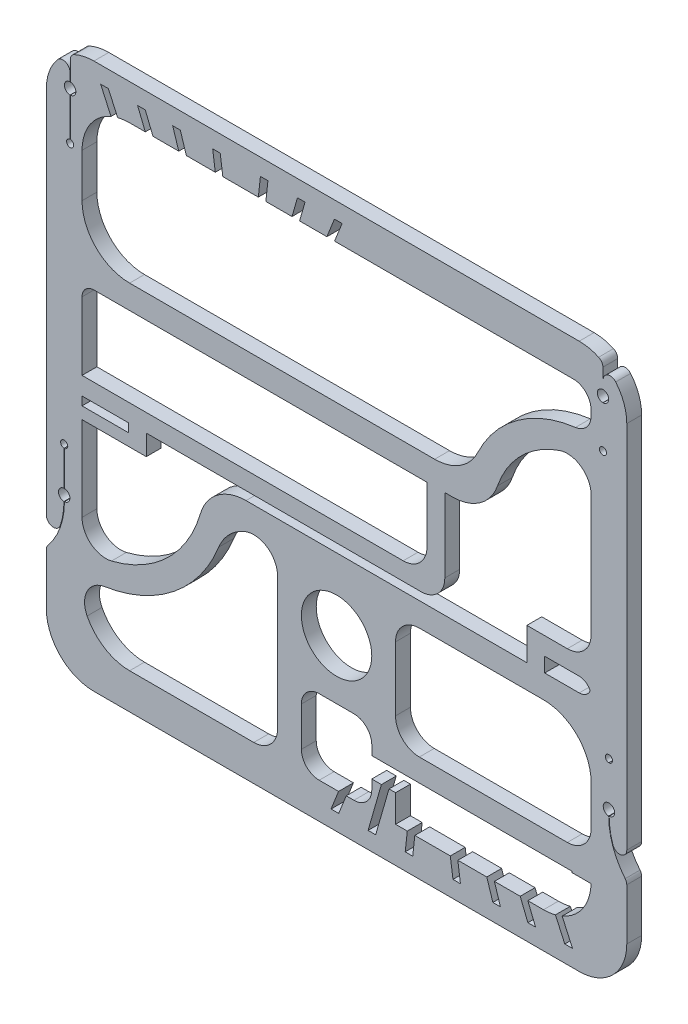
SolidWorks part; units mm, degrees
ref_plane "Front Plane" through (0, 0, 0) normal (0, 0, 1) x (1, 0, 0)
ref_plane "Top Plane" through (0, 0, 0) normal (0, 1, 0) x (1, 0, 0)
ref_plane "Right Plane" through (0, 0, 0) normal (1, 0, 0) x (0, 0, -1)
sketch "Sketch1" plane through (0, 0, 0) normal (0, 0, 1) x (1, 0, 0)
  line L0 (44.642, 21.8842) -> (44.642, 18.0742) construction
  line L1 (-10.1934, 21.8842) -> (51.7832, 21.8842)
  line L2 (-10.1934, 21.8842) -> (-10.1934, -36.406)
  line L3 (-10.1934, -36.406) -> (51.7832, -36.406)
  line L4 (51.7832, 21.8842) -> (51.7832, -36.406)
  line L5 (47.9732, -32.596) -> (-6.3834, -32.596)
  line L6 (47.9732, -32.596) -> (47.9732, 18.0742)
  line L7 (47.9732, 18.0742) -> (-6.3834, 18.0742)
  line L8 (-6.3834, -32.596) -> (-6.3834, 18.0742)
  line L9 (44.642, 19.9792) -> (-35.1587, 19.9792) construction
  line L10 (-6.3834, -31.0517) -> (-10.1934, -31.0517) construction
  line L11 (-8.2884, -31.0517) -> (-8.2884, 6.9585) construction
  line L12 (20.6521, 19.9792) -> (21.1982, 19.9792) construction
  line L14 (3.0779, -32.596) -> (3.0779, -36.406) construction
  line L15 (3.0779, -34.501) -> (37.3423, -34.501) construction
  line L16 (47.9732, -11.8991) -> (47.9732, 12.9942) construction
  line L17 (51.7832, 15.2205) -> (47.9732, 15.2205) construction
  line L18 (49.8782, 15.2205) -> (49.8782, -0.9437) construction
  line L20 (20.9378, -34.501) -> (20.3916, -34.501) construction
  line L21 (-6.3834, 8.0412) -> (-6.3834, -11.8991) construction
  dimension "D1" = 3.81
  dimension "D2" = 3.81
extrude "Boss-Extrude1" add sketch "Sketch1" along normal blind 1.5875
sketch "Sketch2" plane through (0, 0, 0) normal (0, 0, -1) x (-1, 0, 0)
  line L0 (-47.9732, -32.596) -> (-47.9732, 18.0742) construction
  line L1 (-34.8696, 3.2518) -> (6.3834, 3.2518)
  line L2 (-47.9732, 3.653) -> (-47.9732, 0.4065)
  line L3 (-37.4096, 0.7118) -> (6.3834, 0.7118)
  line L4 (6.3834, 3.2518) -> (6.3834, 0.7118)
  line L5 (6.3834, 18.0742) -> (6.3834, -32.596) construction
  line L8 (-47.9732, -13.182) -> (-9.1041, -13.182)
  line L9 (-47.9732, -13.182) -> (-47.9732, -10.642)
  line L10 (-47.9732, -10.642) -> (-6.771, -10.642)
  line L11 (1.357, -21.2563) -> (14.2432, -21.2563) construction
  line L12 (6.3834, -23.7963) -> (6.3834, -26.3363)
  line L13 (-47.9732, 13.8154) -> (-47.9732, 11.2754)
  line L14 (-41.1149, -10.642) -> (-0.4749, -10.642) construction
  line L15 (-40.2005, -1.1932) -> (-39.5655, -1.1932) construction
  arc A0 (-47.9732, 11.2754) -> (-37.4096, 0.7118) centre (-47.9732, 0.7118) cw
  arc A1 (-47.9732, 13.8154) -> (-34.8696, 3.2518) centre (-47.9732, 0.4065) cw
  arc A2 (6.3834, -23.7963) -> (-6.771, -10.642) centre (6.3834, -10.642) cw
  arc A3 (-9.1041, -13.182) -> (6.3834, -26.3363) centre (6.3834, -10.642) ccw
  circle A5 centre (1.357, -18.2591) radius 2.9972 construction
  line M5 (-47.9732, -32.596) -> (-47.9732, 18.0742)
  line M7 (6.3834, 18.0742) -> (6.3834, -32.596)
  dimension "D5" = 2.54
  dimension "D1" = 2.54
  dimension "D2" = 2.54
  dimension "D3" = 2.54
  dimension "D4" = 2.54
  dimension "D6" = 2.54
  dimension "D7" = 2.54
  dimension "D8" = 1.905
extrude "Boss-Extrude2" add sketch "Sketch2" against normal up to surface (1.5875 mm away) contours A1 A0 L3 L1 M5 M7 | L10 L8 M5 M7 region at (14.2431, 2.6927, 0) region at (-5.8176, -25.0663, 0) up to face at (20.7949, -7.2609, 1.5875)
sketch "Sketch3" plane through (0, 0, 0) normal (0, 0, -1) x (-1, 0, 0)
  line L0 (-47.9732, -7.1876) -> (-41.1149, -7.1876)
  line L1 (-47.9732, -10.642) -> (-47.9732, 11.2754) construction
  line L3 (-41.1149, -7.1876) -> (-41.1149, -10.642)
  line L4 (-47.9732, -10.642) -> (-6.771, -10.642) construction
  line L5 (-41.1149, -10.642) -> (-43.0199, -10.642)
  line L6 (-43.0199, -10.642) -> (-43.0199, -9.0926)
  line L7 (-43.0199, -9.0926) -> (-47.9732, -9.0926)
  line L8 (-47.9732, -9.0926) -> (-47.9732, -7.1876)
  line L10 (-32.3519, 0.7118) -> (-32.3519, -9.7276)
  line L11 (-37.4096, 0.7118) -> (6.3834, 0.7118) construction
  line L13 (-32.3519, -9.7276) -> (6.3834, -9.7276)
  line L14 (6.3834, 0.7118) -> (6.3834, -23.7963) construction
  line L15 (6.3834, -9.7276) -> (6.3834, -7.8226)
  line L16 (6.3834, -7.8226) -> (-30.4469, -7.8226)
  line L17 (-30.4469, -7.8226) -> (-30.4469, 0.7118)
  line L18 (-30.4469, 0.7118) -> (-32.3519, 0.7118)
  line L19 (-0.4749, -9.7276) -> (-41.1149, -9.7276) construction
  line L20 (-33.6219, -7.1876) -> (-33.6219, -9.7276) construction
  line L21 (-41.1149, -9.7276) -> (-41.1149, -10.642) construction
  dimension "D1" = 1.905
  dimension "D2" = 1.905
  dimension "D3" = 2.54
  dimension "D4" = 1.905
  dimension "D5" = 1.27
  dimension "D6" = 1.905
extrude "Boss-Extrude3" add sketch "Sketch3" against normal up to surface (1.5875 mm away) up to face at (21.3162, -5.4863, 1.5875)
fillet "Fillet1" radius 5.08 4 edges at (51.7832, -36.406, 0.7937) (-10.1934, -36.406, 0.7937) (-10.1934, 21.8842, 0.7937) (51.7832, 21.8842, 0.7937)
fillet "Fillet2" radius 5.08 9 edges at (9.1041, -13.182, 0.7937) (47.9732, -13.182, 0.7937) (47.9732, -32.596, 0.7937) (-6.3834, -32.596, 0.7937) (34.8696, 3.2518, 0.7937) (-6.3834, 3.2518, 0.7937) (-6.3834, 18.0742, 0.7937) (6.771, -10.642, 0.7937) (37.4096, 0.7118, 0.7937)
fillet "Fillet3" radius 2.54 6 edges at (47.9732, -7.1876, 0.7937) (30.4469, -7.8226, 0.7937) (32.3519, -9.7276, 0.7937) (47.9732, 11.2754, 0.7937) (-6.3834, -26.3363, 0.7937) (-6.3834, -23.7963, 0.7937)
fillet "Fillet4" radius 1.27 3 edges at (47.9732, -10.642, 0.7937) (47.9732, -9.0926, 0.7937) (-6.3834, 0.7118, 0.7937)
sketch "Sketch5" plane through (0, 0, 0) normal (0, 0, -1) x (-1, 0, 0)
  line L0 (-42.8932, -13.182) -> (-12.943, -13.182) construction
  line L1 (-27.0941, -13.182) -> (-14.4957, -13.182)
  line L2 (-27.0941, -13.182) -> (-27.0941, -32.596)
  line L3 (-27.0941, -32.596) -> (-14.4957, -32.596)
  line L4 (-14.4957, -13.182) -> (-14.4957, -32.596)
  line L5 (1.3034, -32.596) -> (-42.8932, -32.596) construction
  line L6 (-24.5541, -18.2972) -> (-27.0941, -18.2972) construction
  line L9 (-17.0357, -18.2972) -> (-14.4957, -18.2972) construction
  circle A1 centre (-20.7949, -18.2972) radius 3.7592 construction
  dimension "D1" = 2.54
extrude "Boss-Extrude4" add sketch "Sketch5" against normal up to surface (1.5875 mm away) up to face at (11.864, -3.3875, 1.5875)
sketch "Sketch6" plane through (0, 0, 0) normal (0, 0, -1) x (-1, 0, 0)
  circle A0 centre (-20.7949, -18.2972) radius 3.7592 construction
  circle A1 centre (-20.7949, -18.2972) radius 3.7592
extrude "Cut-Extrude2" cut sketch "Sketch6" against normal up to surface (1.5875 mm away) up to face at (5.503, -23.566, 1.5875)
sketch "Sketch7" plane through (0, 0, 0) normal (0, 0, -1) x (-1, 0, 0)
  line L0 (-27.0941, -13.182) -> (-27.0941, -32.596) construction
  line L1 (-24.5541, -24.5964) -> (-17.0357, -24.5964)
  line L2 (-24.5541, -24.5964) -> (-24.5541, -32.596)
  line L3 (-24.5541, -32.596) -> (-17.0357, -32.596)
  line L4 (-17.0357, -24.5964) -> (-17.0357, -32.596)
  line L5 (-14.4957, -32.596) -> (-14.4957, -13.182) construction
  line L6 (1.3034, -32.596) -> (-14.4957, -32.596) construction
  line L7 (-20.7949, -22.0564) -> (-6.5424, -22.0564) construction
  line L8 (-20.7949, -22.0564) -> (-20.7949, -21.3452) construction
  circle A0 centre (-20.7949, -18.2972) radius 3.7592 construction
  dimension "D1" = 2.54
  dimension "D2" = 2.54
  dimension "D3" = 2.54
extrude "Cut-Extrude3" cut sketch "Sketch7" against normal up to surface (1.5875 mm away) up to face at (24.5541, -18.2972, 1.5875)
fillet "Fillet5" radius 1.905 4 edges at (24.5541, -32.596, 0.7937) (17.0357, -32.596, 0.7938) (17.0357, -24.5964, 0.7938) (24.5541, -24.5964, 0.7938)
sketch "Sketch8" plane through (0, 0, 0) normal (0, 0, -1) x (-1, 0, 0)
  line L0 (-47.9732, -27.516) -> (-47.9732, -18.262) construction
  line L1 (-47.9732, -25.103) -> (-27.0941, -25.103)
  line L2 (-47.9732, -25.103) -> (-47.9732, -27.643)
  line L3 (-47.9732, -27.643) -> (-27.0941, -27.643)
  line L4 (-27.0941, -25.103) -> (-27.0941, -27.643)
  line L5 (-27.0941, -13.182) -> (-27.0941, -32.596) construction
  line L6 (-45.7916, -27.643) -> (-20.3916, -27.643) construction
  dimension "D1" = 2.54
extrude "Boss-Extrude5" add sketch "Sketch8" against normal up to surface (1.5875 mm away) up to face at (20.7949, -28.5962, 1.5875)
fillet "Fillet6" radius 2.54 5 edges at (27.0941, -13.182, 0.7937) (14.4957, -13.182, 0.7937) (14.4957, -32.596, 0.7937) (27.0941, -25.103, 0.7937) (47.9732, -25.103, 0.7937)
sketch "Sketch4" plane through (0, 0, 0) normal (0, 0, -1) x (-1, 0, 0)
  line L32 (4.2018, 13.1212) -> (4.2018, 15.0262)
  line L33 (4.2018, 15.0262) -> (1.9539, 15.0262)
  line L34 (1.9539, 15.0262) -> (4.2018, 19.9792)
  line L35 (4.2018, 19.9792) -> (3.6556, 19.9792)
  line L36 (3.6556, 19.9792) -> (1.4078, 15.0262)
  line L37 (1.4078, 15.0262) -> (-1.7417, 15.0262)
  line L38 (-1.7417, 15.0262) -> (0.2648, 19.9792)
  line L39 (0.2648, 19.9792) -> (-0.2814, 19.9792)
  line L40 (-0.2814, 19.9792) -> (-2.2879, 15.0262)
  line L41 (-2.2879, 15.0262) -> (-5.0437, 15.0262)
  line L42 (-5.0437, 15.0262) -> (-3.469, 19.9792)
  line L43 (-3.469, 19.9792) -> (-4.0152, 19.9792)
  line L44 (-4.0152, 19.9792) -> (-5.5899, 15.0262)
  line L45 (-5.5899, 15.0262) -> (-8.3965, 15.0262)
  line L46 (-8.3965, 15.0262) -> (-7.7108, 19.9792)
  line L47 (-7.7108, 19.9792) -> (-8.257, 19.9792)
  line L48 (-8.257, 19.9792) -> (-8.9427, 15.0262)
  line L49 (-8.9427, 15.0262) -> (-12.2319, 15.0262)
  line L50 (-12.2319, 15.0262) -> (-12.7781, 19.9792)
  line L51 (-12.7781, 19.9792) -> (-13.3242, 19.9792)
  line L52 (-13.3242, 19.9792) -> (-12.7781, 15.0262)
  line L53 (-12.7781, 15.0262) -> (-15.2926, 15.0262)
  line L54 (-15.2926, 15.0262) -> (-16.7151, 19.9792)
  line L55 (-16.7151, 19.9792) -> (-17.2612, 19.9792)
  line L56 (-17.2612, 19.9792) -> (-15.8388, 15.0262)
  line L57 (-15.8388, 15.0262) -> (-18.6963, 15.0262)
  line L58 (-18.6963, 15.0262) -> (-20.6521, 19.9792)
  line L59 (-20.6521, 19.9792) -> (-21.1982, 19.9792)
  line L60 (-21.1982, 19.9792) -> (-19.2425, 15.0262)
  line L61 (-19.2425, 15.0262) -> (-21.1982, 15.0262)
  line L62 (-21.1982, 15.0262) -> (-21.1982, 13.1212)
  line L63 (-21.1982, 13.1212) -> (4.2018, 13.1212)
  line L64 (4.2018, 13.1212) -> (4.2018, 15.0262) construction
  line L65 (4.2018, 15.0262) -> (1.9539, 15.0262) construction
  line L66 (1.9539, 15.0262) -> (4.2018, 19.9792) construction
  line L67 (4.2018, 19.9792) -> (3.6556, 19.9792) construction
  line L68 (3.6556, 19.9792) -> (1.4078, 15.0262) construction
  line L69 (1.4078, 15.0262) -> (-1.7417, 15.0262) construction
  line L70 (-1.7417, 15.0262) -> (0.2648, 19.9792) construction
  line L71 (0.2648, 19.9792) -> (-0.2814, 19.9792) construction
  line L72 (-0.2814, 19.9792) -> (-2.2879, 15.0262) construction
  line L73 (-2.2879, 15.0262) -> (-5.0437, 15.0262) construction
  line L74 (-5.0437, 15.0262) -> (-3.469, 19.9792) construction
  line L75 (-3.469, 19.9792) -> (-4.0152, 19.9792) construction
  line L76 (-4.0152, 19.9792) -> (-5.5899, 15.0262) construction
  line L77 (-5.5899, 15.0262) -> (-8.3965, 15.0262) construction
  line L78 (-8.3965, 15.0262) -> (-7.7108, 19.9792) construction
  line L79 (-7.7108, 19.9792) -> (-8.257, 19.9792) construction
  line L80 (-8.257, 19.9792) -> (-8.9427, 15.0262) construction
  line L81 (-8.9427, 15.0262) -> (-12.2319, 15.0262) construction
  line L82 (-12.2319, 15.0262) -> (-12.7781, 19.9792) construction
  line L83 (-12.7781, 19.9792) -> (-13.3242, 19.9792) construction
  line L84 (-13.3242, 19.9792) -> (-12.7781, 15.0262) construction
  line L85 (-12.7781, 15.0262) -> (-15.2926, 15.0262) construction
  line L86 (-15.2926, 15.0262) -> (-16.7151, 19.9792) construction
  line L87 (-16.7151, 19.9792) -> (-17.2612, 19.9792) construction
  line L88 (-17.2612, 19.9792) -> (-15.8388, 15.0262) construction
  line L89 (-15.8388, 15.0262) -> (-18.6963, 15.0262) construction
  line L90 (-18.6963, 15.0262) -> (-20.6521, 19.9792) construction
  line L91 (-20.6521, 19.9792) -> (-21.1982, 19.9792) construction
  line L92 (-21.1982, 19.9792) -> (-19.2425, 15.0262) construction
  line L93 (-19.2425, 15.0262) -> (-21.1982, 15.0262) construction
  line L94 (-21.1982, 15.0262) -> (-21.1982, 13.1212) construction
  line L95 (-21.1982, 13.1212) -> (4.2018, 13.1212) construction
  line L96 (-45.7916, -27.643) -> (-45.7916, -29.548)
  line L97 (-45.7916, -29.548) -> (-43.5438, -29.548)
  line L98 (-43.5438, -29.548) -> (-45.7916, -34.501)
  line L99 (-45.7916, -34.501) -> (-45.2455, -34.501)
  line L100 (-45.2455, -34.501) -> (-42.9976, -29.548)
  line L101 (-42.9976, -29.548) -> (-39.8482, -29.548)
  line L102 (-39.8482, -29.548) -> (-41.8546, -34.501)
  line L103 (-41.8546, -34.501) -> (-41.3085, -34.501)
  line L104 (-41.3085, -34.501) -> (-39.302, -29.548)
  line L105 (-39.302, -29.548) -> (-36.5462, -29.548)
  line L106 (-36.5462, -29.548) -> (-38.1208, -34.501)
  line L107 (-38.1208, -34.501) -> (-37.5747, -34.501)
  line L108 (-37.5747, -34.501) -> (-36, -29.548)
  line L109 (-36, -29.548) -> (-33.1934, -29.548)
  line L110 (-33.1934, -29.548) -> (-33.879, -34.501)
  line L111 (-33.879, -34.501) -> (-33.3329, -34.501)
  line L112 (-33.3329, -34.501) -> (-32.6472, -29.548)
  line L113 (-32.6472, -29.548) -> (-29.358, -29.548)
  line L114 (-29.358, -29.548) -> (-28.8118, -34.501)
  line L115 (-28.8118, -34.501) -> (-28.2656, -34.501)
  line L116 (-28.2656, -34.501) -> (-28.8118, -29.548)
  line L117 (-28.8118, -29.548) -> (-26.2973, -29.548)
  line L118 (-26.2973, -29.548) -> (-24.8748, -34.501)
  line L119 (-24.8748, -34.501) -> (-24.3286, -34.501)
  line L120 (-24.3286, -34.501) -> (-25.7511, -29.548)
  line L121 (-25.7511, -29.548) -> (-22.8935, -29.548)
  line L122 (-22.8935, -29.548) -> (-20.9378, -34.501)
  line L123 (-20.9378, -34.501) -> (-20.3916, -34.501)
  line L124 (-20.3916, -34.501) -> (-22.3474, -29.548)
  line L125 (-22.3474, -29.548) -> (-20.3916, -29.548)
  line L126 (-20.3916, -29.548) -> (-20.3916, -27.643)
  line L127 (-20.3916, -27.643) -> (-45.7916, -27.643)
  line L128 (-45.7916, -27.643) -> (-45.7916, -29.548) construction
  line L129 (-45.7916, -29.548) -> (-43.5438, -29.548) construction
  line L130 (-43.5438, -29.548) -> (-45.7916, -34.501) construction
  line L131 (-45.7916, -34.501) -> (-45.2455, -34.501) construction
  line L132 (-45.2455, -34.501) -> (-42.9976, -29.548) construction
  line L133 (-42.9976, -29.548) -> (-39.8482, -29.548) construction
  line L134 (-39.8482, -29.548) -> (-41.8546, -34.501) construction
  line L135 (-41.8546, -34.501) -> (-41.3085, -34.501) construction
  line L136 (-41.3085, -34.501) -> (-39.302, -29.548) construction
  line L137 (-39.302, -29.548) -> (-36.5462, -29.548) construction
  line L138 (-36.5462, -29.548) -> (-38.1208, -34.501) construction
  line L139 (-38.1208, -34.501) -> (-37.5747, -34.501) construction
  line L140 (-37.5747, -34.501) -> (-36, -29.548) construction
  line L141 (-36, -29.548) -> (-33.1934, -29.548) construction
  line L142 (-33.1934, -29.548) -> (-33.879, -34.501) construction
  line L143 (-33.879, -34.501) -> (-33.3329, -34.501) construction
  line L144 (-33.3329, -34.501) -> (-32.6472, -29.548) construction
  line L145 (-32.6472, -29.548) -> (-29.358, -29.548) construction
  line L146 (-29.358, -29.548) -> (-28.8118, -34.501) construction
  line L147 (-28.8118, -34.501) -> (-28.2656, -34.501) construction
  line L148 (-28.2656, -34.501) -> (-28.8118, -29.548) construction
  line L149 (-28.8118, -29.548) -> (-26.2973, -29.548) construction
  line L150 (-26.2973, -29.548) -> (-24.8748, -34.501) construction
  line L151 (-24.8748, -34.501) -> (-24.3286, -34.501) construction
  line L152 (-24.3286, -34.501) -> (-25.7511, -29.548) construction
  line L153 (-25.7511, -29.548) -> (-22.8935, -29.548) construction
  line L154 (-22.8935, -29.548) -> (-20.9378, -34.501) construction
  line L155 (-20.9378, -34.501) -> (-20.3916, -34.501) construction
  line L156 (-20.3916, -34.501) -> (-22.3474, -29.548) construction
  line L157 (-22.3474, -29.548) -> (-20.3916, -29.548) construction
  line L158 (-20.3916, -29.548) -> (-20.3916, -27.643) construction
  line L159 (-20.3916, -27.643) -> (-45.7916, -27.643) construction
  line L263 (4.3288, 12.9942) -> (4.3288, 15.1532)
  line L264 (4.3288, 15.1532) -> (2.151, 15.1532)
  line L265 (2.151, 15.1532) -> (4.3989, 20.1062)
  line L266 (4.3989, 20.1062) -> (3.5738, 20.1062)
  line L267 (3.5738, 20.1062) -> (1.3259, 15.1532)
  line L268 (1.3259, 15.1532) -> (-1.5532, 15.1532)
  line L269 (-1.5532, 15.1532) -> (0.4532, 20.1062)
  line L270 (0.4532, 20.1062) -> (-0.367, 20.1062)
  line L271 (-0.367, 20.1062) -> (-2.3735, 15.1532)
  line L272 (-2.3735, 15.1532) -> (-4.8701, 15.1532)
  line L273 (-4.8701, 15.1532) -> (-3.2954, 20.1062)
  line L274 (-3.2954, 20.1062) -> (-4.1081, 20.1062)
  line L275 (-4.1081, 20.1062) -> (-5.6828, 15.1532)
  line L276 (-5.6828, 15.1532) -> (-8.2507, 15.1532)
  line L277 (-8.2507, 15.1532) -> (-7.565, 20.1062)
  line L278 (-7.565, 20.1062) -> (-8.3676, 20.1062)
  line L279 (-8.3676, 20.1062) -> (-9.0533, 15.1532)
  line L280 (-9.0533, 15.1532) -> (-12.1181, 15.1532)
  line L281 (-12.1181, 15.1532) -> (-12.6643, 20.1062)
  line L282 (-12.6643, 20.1062) -> (-13.466, 20.1062)
  line L283 (-13.466, 20.1062) -> (-12.9198, 15.1532)
  line L284 (-12.9198, 15.1532) -> (-15.1969, 15.1532)
  line L285 (-15.1969, 15.1532) -> (-16.6194, 20.1062)
  line L286 (-16.6194, 20.1062) -> (-17.4298, 20.1062)
  line L287 (-17.4298, 20.1062) -> (-16.0074, 15.1532)
  line L288 (-16.0074, 15.1532) -> (-18.6099, 15.1532)
  line L289 (-18.6099, 15.1532) -> (-20.5657, 20.1062)
  line L290 (-20.5657, 20.1062) -> (-21.3849, 20.1062)
  line L291 (-21.3849, 20.1062) -> (-19.4292, 15.1532)
  line L292 (-19.4292, 15.1532) -> (-21.3252, 15.1532)
  line L293 (-21.3252, 15.1532) -> (-21.3252, 12.9942)
  line L294 (-21.3252, 12.9942) -> (4.3288, 12.9942)
  line L295 (-45.9186, -27.516) -> (-45.9186, -29.675)
  line L296 (-45.9186, -29.675) -> (-43.7409, -29.675)
  line L297 (-43.7409, -29.675) -> (-45.9887, -34.628)
  line L298 (-45.9887, -34.628) -> (-45.1636, -34.628)
  line L299 (-45.1636, -34.628) -> (-42.9158, -29.675)
  line L300 (-42.9158, -29.675) -> (-40.0367, -29.675)
  line L301 (-40.0367, -29.675) -> (-42.0431, -34.628)
  line L302 (-42.0431, -34.628) -> (-41.2229, -34.628)
  line L303 (-41.2229, -34.628) -> (-39.2164, -29.675)
  line L304 (-39.2164, -29.675) -> (-36.7198, -29.675)
  line L305 (-36.7198, -29.675) -> (-38.2945, -34.628)
  line L306 (-38.2945, -34.628) -> (-37.4818, -34.628)
  line L307 (-37.4818, -34.628) -> (-35.9071, -29.675)
  line L308 (-35.9071, -29.675) -> (-33.3392, -29.675)
  line L309 (-33.3392, -29.675) -> (-34.0248, -34.628)
  line L310 (-34.0248, -34.628) -> (-33.2222, -34.628)
  line L311 (-33.2222, -34.628) -> (-32.5366, -29.675)
  line L312 (-32.5366, -29.675) -> (-29.4717, -29.675)
  line L313 (-29.4717, -29.675) -> (-28.9256, -34.628)
  line L314 (-28.9256, -34.628) -> (-28.1239, -34.628)
  line L315 (-28.1239, -34.628) -> (-28.67, -29.675)
  line L316 (-28.67, -29.675) -> (-26.3929, -29.675)
  line L317 (-26.3929, -29.675) -> (-24.9705, -34.628)
  line L318 (-24.9705, -34.628) -> (-24.16, -34.628)
  line L319 (-24.16, -34.628) -> (-25.5825, -29.675)
  line L320 (-25.5825, -29.675) -> (-22.9799, -29.675)
  line L321 (-22.9799, -29.675) -> (-21.0242, -34.628)
  line L322 (-21.0242, -34.628) -> (-20.205, -34.628)
  line L323 (-20.205, -34.628) -> (-22.1607, -29.675)
  line L324 (-22.1607, -29.675) -> (-20.2646, -29.675)
  line L325 (-20.2646, -29.675) -> (-20.2646, -27.516)
  line L326 (-20.2646, -27.516) -> (-45.9186, -27.516)
  dimension "D1" = 0
  dimension "D2" = 0
  dimension "D3" = 0.127
  dimension "D4" = 0.127
extrude "Cut-Extrude1" cut sketch "Sketch4" against normal up to surface (1.5875 mm away) up to face at (37.2819, -19.3942, 1.5875)
sketch "Sketch9" plane through (0, 0, 0) normal (0, 0, -1) x (-1, 0, 0)
  circle A0 centre (-49.2432, 18.0742) radius 0.6096 construction
  circle A1 centre (7.6534, 18.0742) radius 0.6096 construction
  circle A2 centre (8.2884, -19.8366) radius 0.6096 construction
  circle A3 centre (-49.8782, -19.8366) radius 0.6096 construction
  circle A4 centre (-49.2432, 18.0742) radius 0.6096
  circle A5 centre (7.6534, 18.0742) radius 0.6096
  circle A6 centre (8.2884, -19.8366) radius 0.6096
  circle A7 centre (-49.8782, -19.8366) radius 0.6096
extrude "Cut-Extrude4" cut sketch "Sketch9" against normal up to surface (1.5875 mm away) up to face at (31.4097, -31.792, 1.5875)
sketch "Sketch10" plane through (0, 0, 1.5875) normal (0, 0, 1) x (1, 0, 0)
  line L0 (-7.6407, 18.6837) -> (-7.6407, 20.7449) construction
  line L1 (-7.6407, 13.375) -> (-7.6407, 17.4647) construction
  line L2 (-7.6661, 17.4647) -> (-7.6661, 13.375) construction
  line L3 (-7.6661, 19.5715) -> (-7.6661, 18.6837) construction
  line L4 (-7.6407, 18.6837) -> (-7.6407, 20.7449)
  line L5 (-7.6407, 13.375) -> (-7.6407, 17.4647)
  line L6 (-7.6661, 17.4647) -> (-7.6661, 13.375)
  line L7 (-7.6661, 19.5715) -> (-7.6661, 18.6837)
  line L8 (49.2305, 18.6837) -> (49.2305, 20.7449) construction
  line L9 (49.2305, 13.375) -> (49.2305, 17.4647) construction
  line L10 (49.2559, 17.4647) -> (49.2559, 13.375) construction
  line L11 (49.2559, 19.5715) -> (49.2559, 18.6837) construction
  line L12 (49.2305, 18.6837) -> (49.2305, 20.7449)
  line L13 (49.2305, 13.375) -> (49.2305, 17.4647)
  line L14 (49.2559, 17.4647) -> (49.2559, 13.375)
  line L15 (49.2559, 19.5715) -> (49.2559, 18.6837)
  line L16 (49.8909, -15.5181) -> (49.8909, -19.2271) construction
  line L17 (49.8655, -15.5181) -> (49.8655, -19.2271) construction
  line L18 (49.8909, -15.5181) -> (49.8909, -19.2271)
  line L19 (49.8655, -15.5181) -> (49.8655, -19.2271)
  line L20 (-8.2757, -15.5181) -> (-8.2757, -19.2271) construction
  line L21 (-8.3011, -15.5181) -> (-8.3011, -19.2271) construction
  line L22 (-8.2757, -15.5181) -> (-8.2757, -19.2271)
  line L23 (-8.3011, -15.5181) -> (-8.3011, -19.2271)
  line L24 (51.7832, -31.326) -> (51.7832, 16.8042) construction
  line L25 (51.7832, -25.8445) -> (51.7832, -22.639)
  line L26 (-10.1934, 16.8042) -> (-10.1934, -31.326) construction
  line L27 (-10.1934, -22.639) -> (-10.1934, -25.8445)
  arc A1 (-7.1902, 21.4403) -> (-7.6407, 20.7449) centre (-6.8787, 20.7449) ccw construction
  arc A2 (-7.6661, 13.375) -> (-7.6407, 13.375) centre (-7.6534, 12.9942) ccw construction
  arc A3 (-7.6661, 19.5715) -> (-9.013, 20.0598) centre (-8.4281, 19.5715) ccw construction
  arc A4 (-5.1134, 21.8842) -> (-10.1934, 16.8042) centre (-5.1134, 16.8042) ccw construction
  arc A5 (-7.1902, 21.4403) -> (-7.6407, 20.7449) centre (-6.8787, 20.7449) ccw
  arc A6 (-7.6661, 13.375) -> (-7.6407, 13.375) centre (-7.6534, 12.9942) ccw
  arc A7 (-7.6661, 19.5715) -> (-9.013, 20.0598) centre (-8.4281, 19.5715) ccw
  arc A8 (-7.1902, 21.4403) -> (-9.013, 20.0598) centre (-5.1134, 16.8042) ccw
  circle A9 centre (-7.6534, 18.0742) radius 0.6096 construction
  arc A10 (-7.6407, 18.6837) -> (-7.6661, 18.6837) centre (-7.6534, 18.0742) ccw
  arc A11 (-7.6661, 17.4647) -> (-7.6407, 17.4647) centre (-7.6534, 18.0742) ccw
  arc A12 (49.2305, 20.7449) -> (48.7801, 21.4403) centre (48.4685, 20.7449) ccw construction
  arc A13 (49.2305, 13.375) -> (49.2559, 13.375) centre (49.2432, 12.9942) ccw construction
  arc A14 (50.6029, 20.0598) -> (49.2559, 19.5715) centre (50.0179, 19.5715) ccw construction
  arc A15 (49.2305, 20.7449) -> (48.7801, 21.4403) centre (48.4685, 20.7449) ccw
  arc A16 (49.2305, 13.375) -> (49.2559, 13.375) centre (49.2432, 12.9942) ccw
  arc A17 (50.6029, 20.0598) -> (49.2559, 19.5715) centre (50.0179, 19.5715) ccw
  arc A18 (49.8909, -15.5181) -> (49.8655, -15.5181) centre (49.8782, -15.1373) ccw construction
  arc A19 (49.9036, -20.4457) -> (50.2983, -22.8798) centre (57.6041, -20.4462) ccw construction
  arc A20 (49.8528, -20.4457) -> (51.6105, -25.3613) centre (57.6041, -20.4462) ccw construction
  arc A21 (50.2983, -22.8798) -> (51.7832, -22.639) centre (51.0212, -22.639) ccw construction
  arc A22 (51.7832, -25.8445) -> (51.6105, -25.3613) centre (51.0212, -25.8445) ccw construction
  arc A23 (49.8909, -15.5181) -> (49.8655, -15.5181) centre (49.8782, -15.1373) ccw
  arc A24 (49.9036, -20.4457) -> (50.2983, -22.8798) centre (57.6041, -20.4462) ccw
  arc A25 (49.8528, -20.4457) -> (51.6105, -25.3613) centre (57.6041, -20.4462) ccw
  arc A26 (50.2983, -22.8798) -> (51.7832, -22.639) centre (51.0212, -22.639) ccw
  arc A27 (51.7832, -25.8445) -> (51.6105, -25.3613) centre (51.0212, -25.8445) ccw
  arc A28 (-10.1934, -22.639) -> (-8.7084, -22.8798) centre (-9.4314, -22.639) ccw construction
  arc A29 (-10.0206, -25.3613) -> (-8.263, -20.4457) centre (-16.0142, -20.4462) ccw construction
  arc A30 (-8.7084, -22.8798) -> (-8.3138, -20.4457) centre (-16.0142, -20.4462) ccw construction
  arc A31 (-8.2757, -15.5181) -> (-8.3011, -15.5181) centre (-8.2884, -15.1373) ccw construction
  arc A32 (-10.1934, -22.639) -> (-8.7084, -22.8798) centre (-9.4314, -22.639) ccw
  arc A33 (-10.0206, -25.3613) -> (-8.263, -20.4457) centre (-16.0142, -20.4462) ccw
  arc A34 (-8.7084, -22.8798) -> (-8.3138, -20.4457) centre (-16.0142, -20.4462) ccw
  arc A35 (-8.2757, -15.5181) -> (-8.3011, -15.5181) centre (-8.2884, -15.1373) ccw
  arc A36 (51.7832, 16.8042) -> (46.7032, 21.8842) centre (46.7032, 16.8042) ccw construction
  arc A37 (50.6029, 20.0598) -> (48.7801, 21.4403) centre (46.7032, 16.8042) ccw
  circle A38 centre (49.2432, 18.0742) radius 0.6096 construction
  arc A39 (49.2559, 18.6837) -> (49.2305, 18.6837) centre (49.2432, 18.0742) ccw
  arc A40 (49.2305, 17.4647) -> (49.2559, 17.4647) centre (49.2432, 18.0742) ccw
  circle A41 centre (49.8782, -19.8366) radius 0.6096 construction
  arc A42 (49.8909, -19.2271) -> (49.8655, -19.2271) centre (49.8782, -19.8366) ccw
  arc A43 (49.8528, -20.4457) -> (49.9036, -20.4457) centre (49.8782, -19.8366) ccw
  circle A44 centre (-8.2884, -19.8366) radius 0.6096 construction
  arc A45 (-8.2757, -19.2271) -> (-8.3011, -19.2271) centre (-8.2884, -19.8366) ccw
  arc A46 (-8.3138, -20.4457) -> (-8.263, -20.4457) centre (-8.2884, -19.8366) ccw
  arc A47 (-10.0206, -25.3613) -> (-10.1934, -25.8445) centre (-9.4314, -25.8445) ccw construction
  arc A48 (-10.0206, -25.3613) -> (-10.1934, -25.8445) centre (-9.4314, -25.8445) ccw
extrude "Slots for carbon" cut sketch "Sketch10" against normal through all
fillet "Fillet7" radius 1.905 2 edges at (47.9732, 13.8154, 0.7937) (47.9732, 18.0742, 0.7937)
sketch "Sketch11" plane through (0, 0, 0) normal (0, 0, -1) x (-1, 0, 0)
  line L0 (-0.4749, -9.7276) -> (-0.4749, -11.912)
  line L1 (-29.8119, -9.7276) -> (6.3834, -9.7276) construction
  line L2 (-0.4749, -11.912) -> (6.3834, -11.912)
  line L3 (6.3834, -9.7276) -> (6.3834, -20.9479) construction
  line L4 (6.3834, -11.912) -> (6.3834, -10.642)
  line L5 (6.3834, -10.642) -> (1.4301, -10.642)
  line L6 (1.4301, -10.642) -> (1.4301, -9.7276)
  line L7 (1.4301, -9.7276) -> (-0.4749, -9.7276)
  line L11 (-0.4749, -9.7276) -> (-0.4749, -10.642) construction
  line L12 (-41.1149, -10.642) -> (-0.4749, -10.642) construction
  dimension "D1" = 1.27
  dimension "D2" = 1.905
  dimension "D3" = 1.27
extrude "Boss-Extrude6" add sketch "Sketch11" against normal up to surface (1.5875 mm away) up to face at (20.7949, -2.3483, 1.5875)
